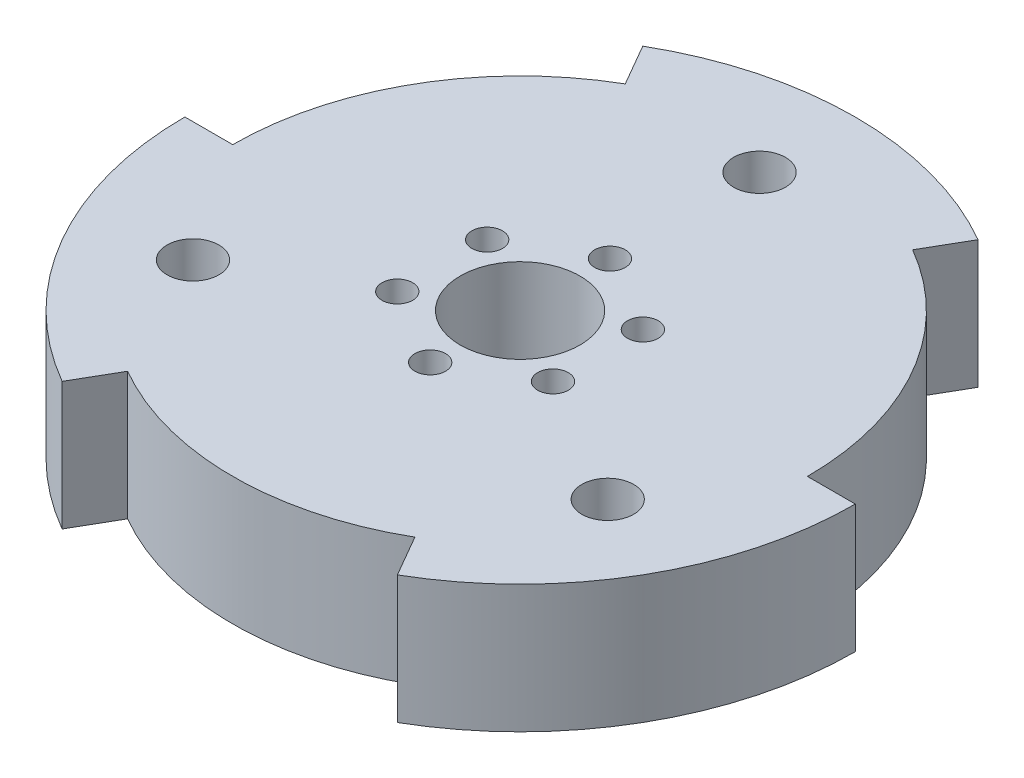
SolidWorks part; units mm, degrees
ref_plane "Front Plane" through (0, 0, 0) normal (0, 0, 1) x (1, 0, 0)
ref_plane "Top Plane" through (0, 0, 0) normal (0, 1, 0) x (1, 0, 0)
ref_plane "Right Plane" through (0, 0, 0) normal (1, 0, 0) x (0, 0, -1)
sketch "Sketch1" plane through (0, 0, 0) normal (0, 1, 0) x (1, 0, 0)
  line L0 (0, 0) -> (0, 35.4208) construction
  line L1 (-20, -20) -> (20, -20)
  line L2 (-20, -20) -> (-20, 20)
  line L3 (-20, 20) -> (20, 20)
  line L4 (20, -20) -> (20, 20)
  line L5 (-20, -20) -> (20, 20) construction
  line L6 (-20, 20) -> (20, -20) construction
  line L7 (17.5, 30.3109) -> (15, 25.9808)
  line L8 (-17.5, 30.3109) -> (-15, 25.9808)
  line L9 (17.5, -30.3109) -> (15, -25.9808)
  line L10 (35, 0) -> (30, 0)
  line L11 (-35, 0) -> (-30, 0)
  line L12 (-17.5, -30.3109) -> (-15, -25.9808)
  circle A0 centre (0, 0) radius 6.25
  circle A1 centre (0, 25) radius 2.7073
  circle A2 centre (21.6506, -12.5) radius 2.7073
  circle A3 centre (-21.6506, -12.5) radius 2.7073
  circle A4 centre (0, 0) radius 30
  arc A5 (17.5, 30.3109) -> (-17.5, 30.3109) centre (0, 0) ccw
  arc A6 (17.5, -30.3109) -> (35, 0) centre (0, 0) ccw
  arc A7 (-35, 0) -> (-17.5, -30.3109) centre (0, 0) ccw
  point P0 (0, 0)
  point P18 (0, 0)
  point P21 (0, 35)
  point P34 (0, 0)
  dimension "D2" = 12.5
  dimension "D6" = 60
  dimension "D7" = 5
  dimension "D8" = 35
  dimension "D9" = 3
  dimension "D1" = 25
  dimension "D3" = 40
  dimension "D4" = 40
  dimension "D5" = 3
extrude "Boss-Extrude1" add sketch "Sketch1" along normal blind 13.35 contours L11 A7 L12 A4 | L9 A6 L10 A4 | L7 A5 L8 A4 | L2 A3 | L4 A2 | A1 | L2 A3 | L4 A2 | A0 | A4 region at (-21.9823, 0, 12.5) region at (-19.5694, 0, 12.5) region at (19.5694, 0, 12.5) region at (21.9823, 0, 12.5) region at (0, 0, -31.0964) region at (26.9303, 0, 15.5482) region at (-26.9303, 0, 15.5482) region at (0, 0, 0) region at (0, 0, -25)
sketch "Sketch5" [suppressed] plane through (0, 0, 0) normal (1, 0, 0) x (0, 0, -1)
  line L0 (-10.331, 15) -> (10.331, 0) construction
  line L1 (10, 5) -> (-10, 5)
  line L2 (10, 5) -> (10, 10)
  line L3 (10, 10) -> (-10, 10)
  line L4 (-10, 5) -> (-10, 10)
  line L5 (10, 5) -> (-10, 10) construction
  line L6 (10, 10) -> (-10, 5) construction
  line L7 (20, 7.5) -> (-20, 7.5) construction
  line L8 (20, 15) -> (20, 0) construction
  line L9 (-20, 15) -> (-20, 0) construction
  line L10 (-10.3541, 15) -> (-10.3078, 15) construction
  line L11 (-10.3541, 0) -> (20, 0) construction
  point P0 (0, 7.5)
  dimension "D1" = 20
  dimension "D2" = 5
sketch "Sketch3" [suppressed] plane through (0, 0, -20) normal (0, 0, -1) x (-1, 0, 0)
  line L3 (15.1539, 15) -> (15.1539, 3) construction
  line L4 (20, 15) -> (10.3078, 15) construction
  circle A0 centre (15.1539, 3) radius 1.6
  dimension "D2" = 3.2
  dimension "D1" = 12
sketch "Sketch2" [suppressed] plane through (0, 0, 20) normal (0, 0, 1) x (1, 0, 0)
  line L0 (0, 27.8717) -> (0, -11.9207) construction
  line L1 (20, 2) -> (10, 2)
  line L3 (10, 2) -> (10, 0)
  line L4 (-20, 0) -> (20, 0) construction
  line L5 (20, 15) -> (20, 0) construction
  circle A0 centre (10, 2) radius 1.6
  circle A1 centre (-10, 2) radius 1.6
  dimension "D3" = 3.2
  dimension "D1" = 10
  dimension "D2" = 2
sketch "Sketch6" plane through (0, 13.35, 0) normal (0, 1, 0) x (1, 0, 0)
  circle A9 centre (0, -9.385) radius 1.6
  circle A10 centre (-8.1276, -4.6925) radius 1.6
  circle A11 centre (-8.1276, 4.6925) radius 1.6
  circle A12 centre (0, 9.385) radius 1.6
  circle A13 centre (8.1276, 4.6925) radius 1.6
  circle A14 centre (8.1276, -4.6925) radius 1.6
  point P3 (0, 0)
  point P16 (0, 0)
  dimension "D2" = 9.385
  dimension "D1" = 3.2
  dimension "D3" = 9.385
extrude "Cut-Extrude1" cut sketch "Sketch6" along normal through all and the other way through all
fillet "Fillet2" [suppressed] radius 5
